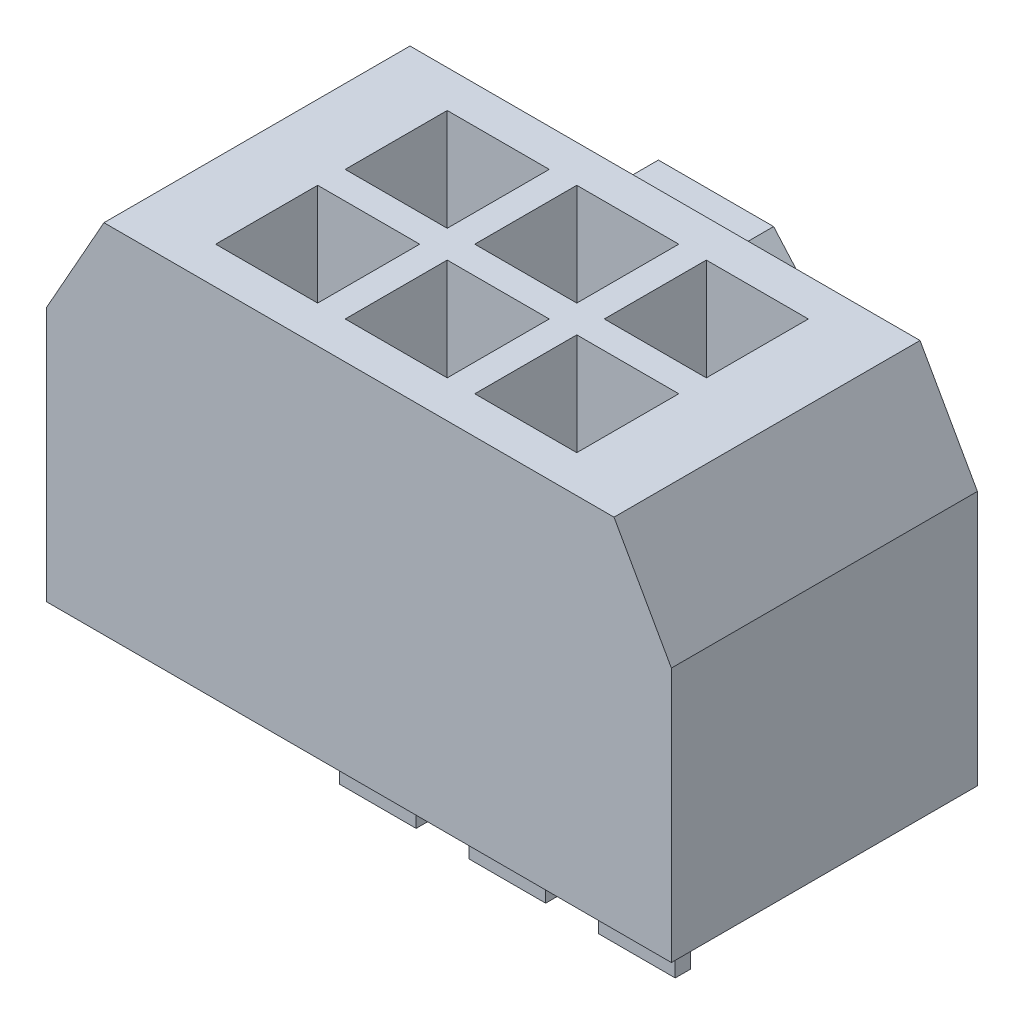
SolidWorks part; units mm, degrees
ref_plane "Front" through (0, 0, 0) normal (0, 0, 1) x (1, 0, 0)
ref_plane "Top" through (0, 0, 0) normal (0, 1, 0) x (1, 0, 0)
ref_plane "Right" through (0, 0, 0) normal (1, 0, 0) x (0, 0, -1)
sketch "Эскиз1" plane through (0, 0, 0) normal (0, 0, 1) x (1, 0, 0)
  line L0 (0, 5.8423) -> (0, -4.6539) construction
  line L1 (-9.0888, 0) -> (10.6015, 0) construction
  line L2 (-6.125, -3.5) -> (6.125, -3.5)
  line L3 (-6.125, -3.5) -> (-6.125, 3.5) construction
  line L4 (-6.125, -3.5) -> (-6.125, 1.5)
  line L5 (-6.125, 1.5) -> (-5, 3.5)
  line L6 (-5, 3.5) -> (5, 3.5)
  line L7 (6.125, -3.5) -> (6.125, 1.5)
  line L8 (6.125, 1.5) -> (5, 3.5)
  line L9 (-1.9, -3.5) -> (-1.9, 2.1221)
  line L10 (-1.9, 2.1221) -> (-1.1294, 2.999)
  line L11 (-1.1294, 2.999) -> (1.1294, 2.999)
  line L12 (1.9, 2.1221) -> (1.1294, 2.999)
  line L13 (1.9, -3.5) -> (1.9, 2.1221)
  point P5 (0, -3.5)
  point P6 (-6.125, 0)
  point P17 (0, 3.5)
  point P19 (0, 0)
  point P21 (0, 2.999)
  dimension "D1" = 12.25
  dimension "D2" = 7
  dimension "D3" = 5
  dimension "D4" = 5
  dimension "D5" = 1.9
extrude "Бобышка-Вытянуть1" add sketch "Эскиз1" along normal mid plane 6 contours L13 L2 L7 L8 L6 L5 L4 L9 L10 L11 L12 | L2 L13 L12 L11 L10 L9 region at (-5.9839, -1, 0) region at (0, -0.3337, 0)
extrude "Бобышка-Вытянуть2" add sketch "Эскиз1<3>" against normal blind 1 from surface contours L2 L13 L12 L11 L10 L9 region at (0, -0.3337, 0) starting at face at (0, 0.5, -3)
sketch "Эскиз1<3>" plane through (0, 0, 0) normal (0, 0, 1) x (1, 0, 0) same geometry as "Эскиз1"
sketch "Эскиз2" plane through (0, 3.5, 0) normal (0, 1, 0) x (1, 0, 0)
  line L0 (-7.3042, 0) -> (8.5138, 0) construction
  line L1 (0, 4.9009) -> (0, -4.5922) construction
  line L2 (-1, 2.27) -> (1, 2.27)
  line L3 (-1, 2.27) -> (-1, 0.27)
  line L4 (-1, 0.27) -> (1, 0.27)
  line L5 (1, 2.27) -> (1, 0.27)
  line L6 (-7.3042, 1.27) -> (8.4447, 1.27) construction
  line L8 (-1, -0.27) -> (1, -0.27)
  line L9 (1, -2.27) -> (1, -0.27)
  line L10 (-1, -2.27) -> (1, -2.27)
  line L11 (-1, -2.27) -> (-1, -0.27)
  line L12 (1.54, 2.27) -> (3.54, 2.27)
  line L13 (1.54, 2.27) -> (1.54, 0.27)
  line L14 (1.54, 0.27) -> (3.54, 0.27)
  line L15 (3.54, 2.27) -> (3.54, 0.27)
  line L16 (1.54, -0.27) -> (3.54, -0.27)
  line L17 (3.54, -2.27) -> (3.54, -0.27)
  line L18 (1.54, -2.27) -> (3.54, -2.27)
  line L19 (1.54, -2.27) -> (1.54, -0.27)
  line L20 (-3.54, 2.27) -> (-1.54, 2.27)
  line L21 (-3.54, 2.27) -> (-3.54, 0.27)
  line L22 (-3.54, 0.27) -> (-1.54, 0.27)
  line L23 (-1.54, 2.27) -> (-1.54, 0.27)
  line L24 (-3.54, -0.27) -> (-1.54, -0.27)
  line L25 (-1.54, -2.27) -> (-1.54, -0.27)
  line L26 (-3.54, -2.27) -> (-1.54, -2.27)
  line L27 (-3.54, -2.27) -> (-3.54, -0.27)
  point P9 (0, 2.27)
  point P12 (-1, 1.27)
  dimension "D1" = 2
  dimension "D2" = 2
  dimension "D3" = 1.27
  dimension "D4" = 2
extrude "Вырез-Вытянуть1" cut sketch "Эскиз2" against normal blind 3
sketch "Эскиз3" plane through (0, -3.5, 0) normal (0, -1, 0) x (1, 0, 0)
  line L0 (-7.0277, 0) -> (7.9608, 0) construction
  line L1 (0, 4.0853) -> (0, -4.7166) construction
  line L2 (-0.115, 0.725) -> (1.385, 0.725)
  line L3 (-0.115, 0.725) -> (-0.115, 0.425)
  line L4 (-0.115, 0.425) -> (1.385, 0.425)
  line L5 (1.385, 0.725) -> (1.385, 0.425)
  line L6 (-1.385, -0.425) -> (0.115, -0.425)
  line L7 (-1.385, -0.425) -> (-1.385, -0.725)
  line L8 (-1.385, -0.725) -> (0.115, -0.725)
  line L9 (0.115, -0.425) -> (0.115, -0.725)
  line L10 (2.425, 0.725) -> (3.925, 0.725)
  line L11 (2.425, 0.725) -> (2.425, 0.425)
  line L12 (2.425, 0.425) -> (3.925, 0.425)
  line L13 (3.925, 0.725) -> (3.925, 0.425)
  line L14 (1.155, -0.425) -> (2.655, -0.425)
  line L15 (1.155, -0.425) -> (1.155, -0.725)
  line L16 (1.155, -0.725) -> (2.655, -0.725)
  line L17 (2.655, -0.425) -> (2.655, -0.725)
  line L18 (-2.655, 0.725) -> (-1.155, 0.725)
  line L19 (-2.655, 0.725) -> (-2.655, 0.425)
  line L20 (-2.655, 0.425) -> (-1.155, 0.425)
  line L21 (-1.155, 0.725) -> (-1.155, 0.425)
  line L22 (-3.925, -0.425) -> (-2.425, -0.425)
  line L23 (-3.925, -0.425) -> (-3.925, -0.725)
  line L24 (-3.925, -0.725) -> (-2.425, -0.725)
  line L25 (-2.425, -0.425) -> (-2.425, -0.725)
  line L26 (-1.385, -0.425) -> (-1.385, -0.725)
  point P9 (1.385, 0.575)
  point P14 (0.115, -0.575)
  point P17 (-0.635, -0.725)
  point P18 (0.635, 0.425)
  point P19 (0.635, 0.725)
  dimension "D1" = 1.5
  dimension "D2" = 0.3
  dimension "D3" = 0.575
  dimension "D4" = 1.15
  dimension "D5" = 1.27
  dimension "D6" = 0.635
extrude "Бобышка-Вытянуть3" add sketch "Эскиз3" along normal blind 2.5 from surface contours L25 L22 L23 L24 | L21 L18 L19 L20 | L9 L6 L7 L8 | L5 L2 L3 L4 | L17 L14 L15 L16 | L13 L10 L11 L12 region at (0.635, -3.5, 0.575) region at (-0.635, -3.5, -0.575) region at (3.175, -3.5, 0.575) region at (1.905, -3.5, -0.575) region at (-1.905, -3.5, 0.575) region at (-3.175, -3.5, -0.575) starting at face at (0, -3.5, -1.75)
